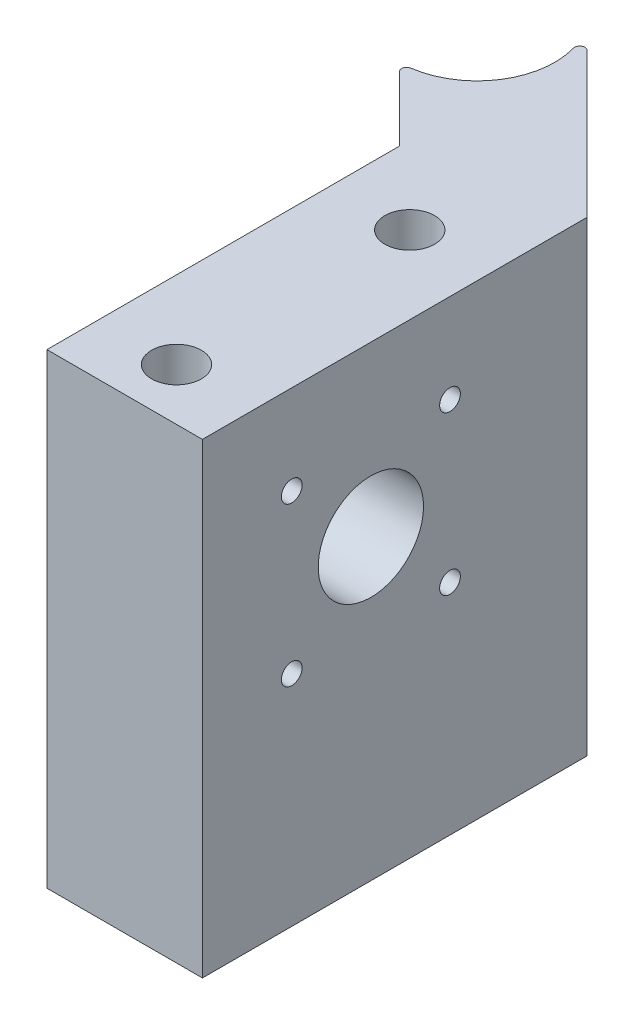
SolidWorks part; units mm, degrees
ref_plane "Front Plane" through (0, 0, 0) normal (0, 0, 1) x (1, 0, 0)
ref_plane "Top Plane" through (0, 0, 0) normal (0, 1, 0) x (1, 0, 0)
ref_plane "Right Plane" through (0, 0, 0) normal (1, 0, 0) x (0, 0, -1)
sketch "Sketch1" plane through (0, 0, 0) normal (0, 1, 0) x (1, 0, 0)
  line L0 (-14.5, 51) -> (7.5, 51) construction
  line L1 (7.5, 51) -> (7.5, 32.1066) construction
  line L2 (7.5, -5) -> (-7.5, -5)
  line L3 (-7.5, -5) -> (-7.5, 29)
  line L4 (-7.5, 36) -> (-14.5, 36) construction
  line L5 (0, 0) -> (0, -5) construction
  line L6 (-14.5, 36) -> (-7.5, 29)
  line L7 (-9.1967, 48.8033) -> (7.5, 32.1066)
  line L8 (-7.5, 29) -> (-7.5, 36) construction
  line L9 (7.5, 32.1066) -> (7.5, -5)
  circle A0 centre (0, 22.5) radius 2.4
  circle A1 centre (0, 0) radius 2.4
  arc A2 (-14.5, 36) -> (-9.1967, 48.8033) centre (-14.5, 43.5) ccw
  arc A3 (-9.1967, 48.8033) -> (-14.5, 51) centre (-14.5, 43.5) ccw construction
  dimension "D2" = 4.8
  dimension "D3" = 15
  dimension "D1" = 22.5
  dimension "D4" = 14.5
  dimension "D5" = 21
  dimension "D6" = 15
  dimension "D7" = 5
  dimension "D8" = 45
extrude "Boss-Extrude1" add sketch "Sketch1" along normal blind 45 contours A2 L6 L3 L2 L9 L7 A1 A0 region at (-0.8967, 0, -18.6724)
sketch "Sketch2" plane through (7.5, 0, 0) normal (1, 0, 0) x (0, 0, -1)
  line L0 (3.617, 36.383) -> (18.883, 21.117) construction
  line L1 (3.617, 36.383) -> (18.883, 36.383) construction
  line L2 (3.617, 36.383) -> (3.617, 21.117) construction
  line L3 (3.617, 21.117) -> (18.883, 21.117) construction
  line L4 (18.883, 36.383) -> (18.883, 21.117) construction
  line L6 (-5, 45) -> (-5, 0) construction
  line L8 (32.1066, 45) -> (-5, 45) construction
  circle A0 centre (11.25, 28.75) radius 5.08
  circle A1 centre (3.617, 36.383) radius 1
  circle A2 centre (18.883, 36.383) radius 1
  circle A3 centre (18.883, 21.117) radius 1
  circle A4 centre (3.617, 21.117) radius 1
  point P14 (14.4676, 45)
  point P16 (-5, 42.1375)
  dimension "D1" = 10.16
  dimension "D3" = 2
  dimension "D5" = 16.25
  dimension "D2" = 15.266
  dimension "D4" = 16.25
extrude "Cut-Extrude1" cut sketch "Sketch2" against normal up to next
fillet "Fillet1" radius 0.5 2 edges at (-9.1967, 22.5, -48.8033) (-14.5, 22.5, -36)
ref_plane "Plane1" through (0, 22.5, 0) normal (0, 1, 0) x (1, 0, 0)
sketch "Sketch3" plane through (0, 22.5, 0) normal (0, 1, 0) x (1, 0, 0)
  line L0 (-8.136, 37.136) -> (-2.8327, 42.4393)
  line L1 (-6.4581, 46.0647) -> (7.5, 32.1066) construction
  line L2 (-1.7721, 41.3787) -> (-7.0754, 36.0754)
  line L3 (-13.7263, 35.2263) -> (-7.5, 29) construction
  line L4 (-13.1083, 34.6083) -> (-11.842, 33.342)
  line L5 (-2.8327, 42.4393) -> (-1.7721, 41.3787)
  arc A0 (-13.1083, 34.6083) -> (-8.136, 37.136) centre (-14.5, 43.5) ccw
  arc A1 (-7.0754, 36.0754) -> (-11.842, 33.342) centre (-14.5, 43.5) cw
  dimension "D1" = 18
  dimension "D2" = 1.5
extrude "Cut-Extrude2" cut sketch "Sketch3" against normal mid plane 4
extrude "Cut-Extrude3" cut sketch "Sketch3<2>" against normal mid plane 4 from offset 17
sketch "Sketch3<2>" plane through (0, 22.5, 0) normal (0, 1, 0) x (1, 0, 0) same geometry as "Sketch3"
mirror "Mirror1" about plane through (0, 22.5, 0) normal (0, 1, 0) of "Cut-Extrude3"
